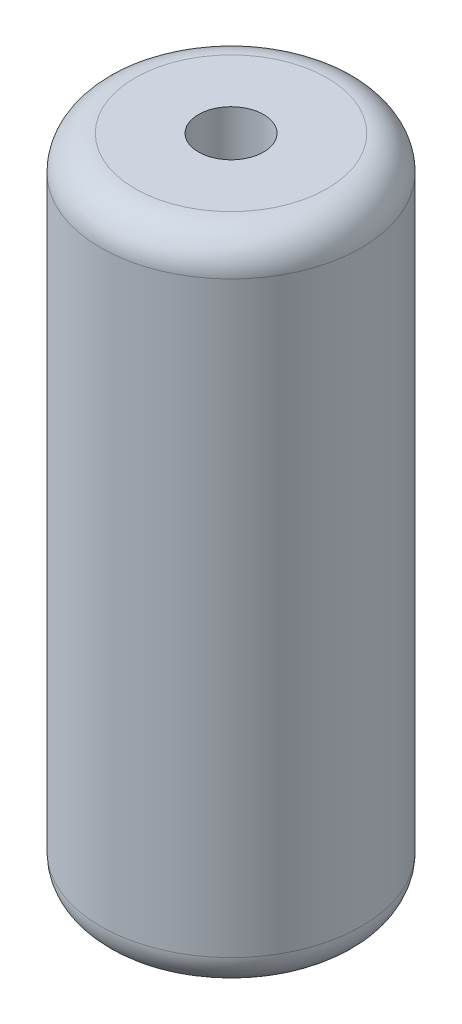
SolidWorks part; units mm, degrees
ref_plane "Alzado" through (0, 0, 0) normal (0, 0, 1) x (1, 0, 0)
ref_plane "Planta" through (0, 0, 0) normal (0, 1, 0) x (1, 0, 0)
ref_plane "Vista lateral" through (0, 0, 0) normal (1, 0, 0) x (0, 0, -1)
sketch "Croquis1" plane through (0, 0, 0) normal (0, 1, 0) x (1, 0, 0)
  circle A0 centre (0, 0) radius 19.05
  circle A1 centre (0, 0) radius 4.7625
  dimension "D1" = 38.1
  dimension "D2" = 9.525
extrude "Saliente-Extruir1" add sketch "Croquis1" along normal blind 96
fillet "Redondeo1" radius 5 2 edges at (0, 0, 19.05) (0, 96, 19.05)
